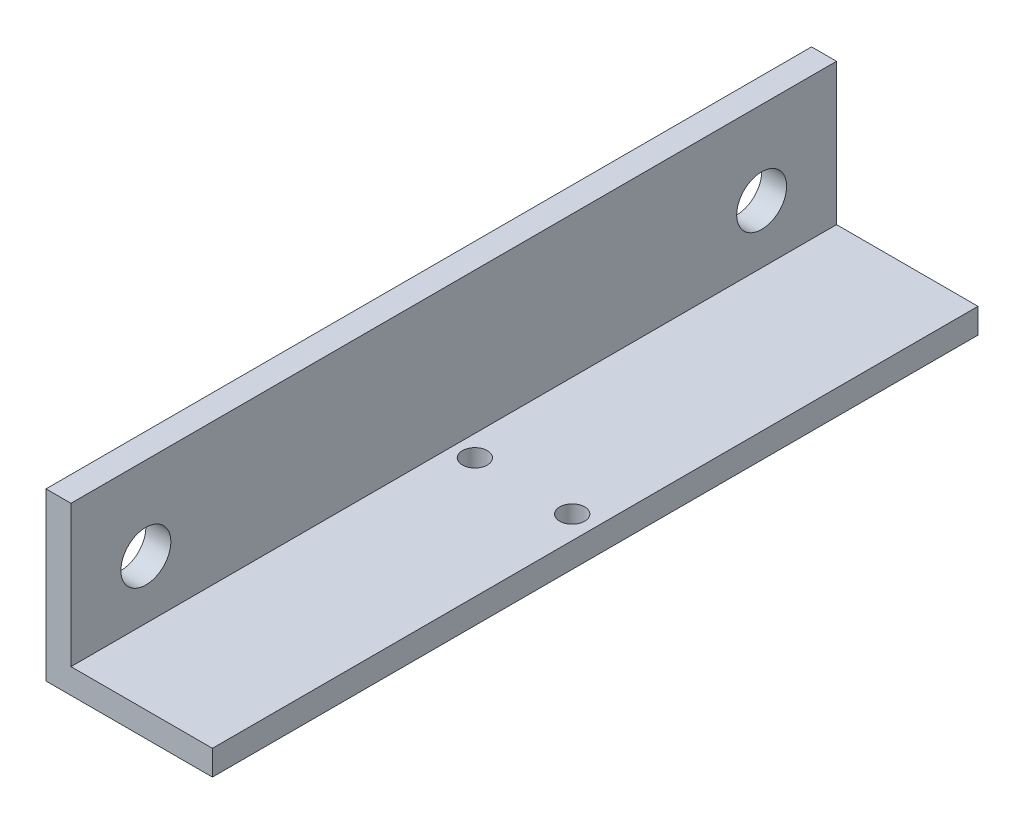
SolidWorks part; units mm, degrees
ref_plane "Front Plane" through (0, 0, 0) normal (0, 0, 1) x (1, 0, 0)
ref_plane "Top Plane" through (0, 0, 0) normal (0, 1, 0) x (1, 0, 0)
ref_plane "Right Plane" through (0, 0, 0) normal (1, 0, 0) x (0, 0, -1)
sketch "Sketch1" plane through (0, 0, 0) normal (0, 0, 1) x (1, 0, 0)
  line L0 (0, 0) -> (10, 0)
  line L1 (0, 0) -> (0, 10)
extrude "Extrude-Thin1" add sketch "Sketch1" along normal blind 46 thin thin type one direction wall 1.5
sketch "Sketch2" plane through (0, 1.5, 0) normal (0, 1, 0) x (1, 0, 0)
  line L0 (10, -23) -> (19.3168, -23) construction
  circle A0 centre (8.6188, -23) radius 0.75
  circle A1 centre (2.7688, -23) radius 0.75
  dimension "D1" = 5.85
extrude "Cut-Extrude1" cut sketch "Sketch2" against normal through all
sketch "Sketch3" plane through (0, 0, 0) normal (-1, 0, 0) x (0, 0, 1)
  line L0 (23, 10) -> (23, 22.0484) construction
  circle A0 centre (41.5, 5) radius 1.5
  circle A1 centre (4.5, 5) radius 1.5
  dimension "D1" = 18.5
extrude "Cut-Extrude2" cut sketch "Sketch3" against normal through all
